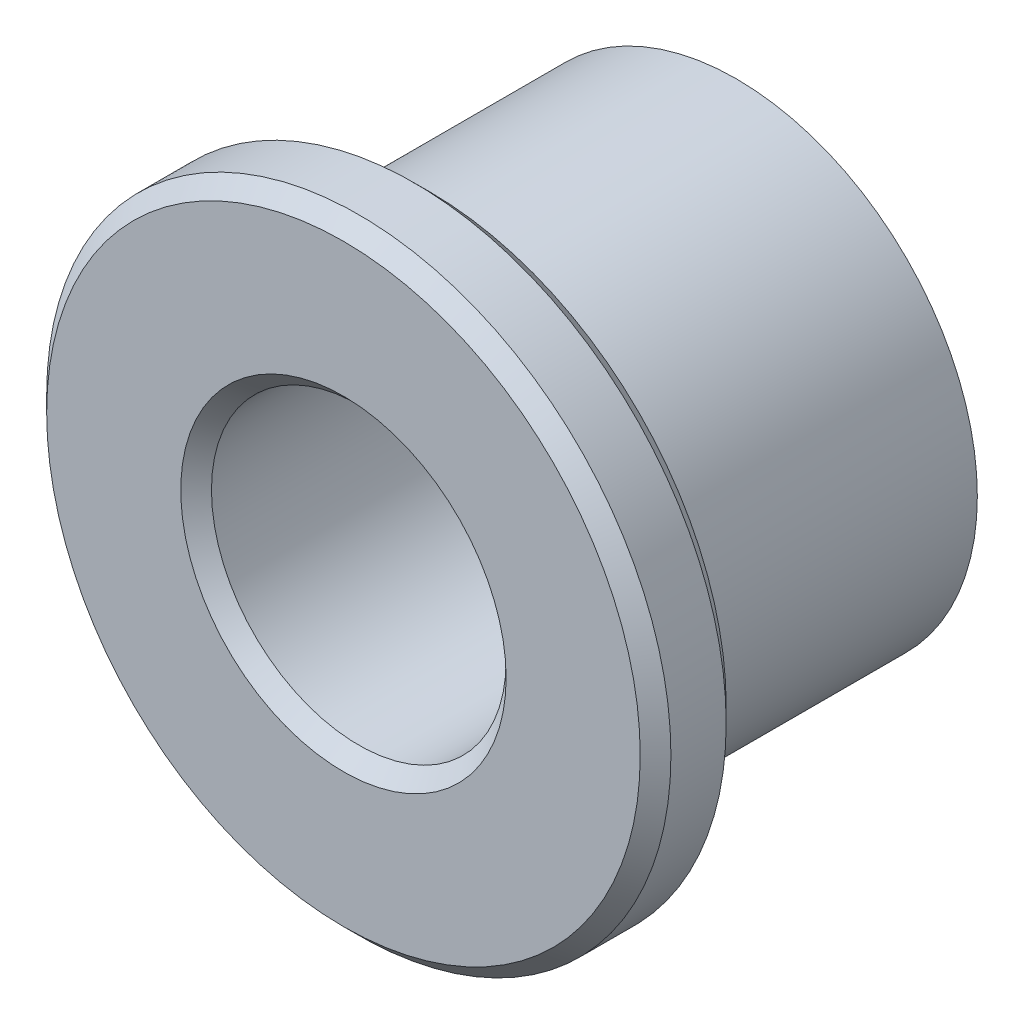
SolidWorks part; units mm, degrees
material "Commercial Bronze, UNS C22000 (90-10 Bronze)"
ref_plane "Front Plane" through (0, 0, 0) normal (0, 0, 1) x (1, 0, 0)
ref_plane "Top Plane" through (0, 0, 0) normal (0, 1, 0) x (1, 0, 0)
ref_plane "Right Plane" through (0, 0, 0) normal (1, 0, 0) x (0, 0, -1)
sketch "Sketch1" plane through (0, 0, 0) normal (0, 0, 1) x (1, 0, 0)
  circle A0 centre (0, 0) radius 3.925
  dimension "D1" = 7.85
extrude "Boss-Extrude1" add sketch "Sketch1" against normal blind 11
sketch "Sketch2" plane through (0, 0, 0) normal (0, 0, 1) x (1, 0, 0)
  circle A0 centre (0, 0) radius 5.0841
extrude "Boss-Extrude2" add sketch "Sketch2" along normal blind 1.4
sketch "Sketch3" plane through (0, 0, 1.4) normal (0, 0, 1) x (1, 0, 0)
  circle A0 centre (0, 0) radius 2.4
  dimension "D1" = 4.8
extrude "Cut-Extrude1" cut sketch "Sketch3" against normal through all
chamfer "Chamfer1" distance 0.25 angle 45 5 edges at (5.0841, 0, 0) (5.0841, 0, 1.4) (3.925, 0, -11) (2.4, 0, -11) (2.4, 0, 1.4)
sketch "Sketch4" plane through (0, 0, -11) normal (0, 0, -1) x (-1, 0, 0)
  circle A0 centre (0, 0) radius 6.1159
extrude "Cut-Extrude2" cut sketch "Sketch4" against normal up to surface (6 mm away)
